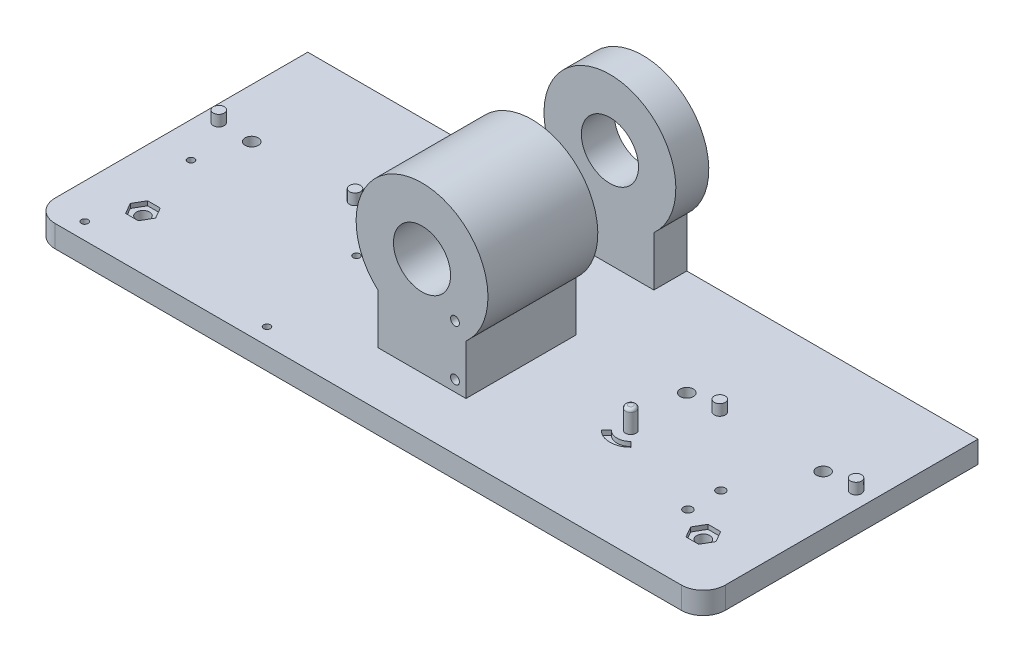
SolidWorks part; units mm, degrees
ref_plane "Front Plane" through (0, 0, 0) normal (0, 0, 1) x (1, 0, 0)
ref_plane "Top Plane" through (0, 0, 0) normal (0, 1, 0) x (1, 0, 0)
ref_plane "Right Plane" through (0, 0, 0) normal (1, 0, 0) x (0, 0, -1)
sketch "Sketch1" plane through (0, 0, 0) normal (0, 1, 0) x (1, 0, 0)
  line L0 (152.5, 125) -> (152.5, 0) construction
  line L1 (0, 0) -> (305, 0)
  line L2 (0, 0) -> (0, 125)
  line L3 (0, 125) -> (305, 125)
  line L4 (305, 0) -> (305, 125)
  line L5 (25, 100) -> (280, 100) construction
  line L6 (280, 25) -> (280, 100) construction
  line L7 (25, 25) -> (280, 25) construction
  line L8 (25, 25) -> (25, 100) construction
  line L9 (152.5, 62.5) -> (25, 62.5) construction
  line L10 (30.7735, 100) -> (27.8868, 105) construction
  line L11 (27.8868, 105) -> (22.1132, 105) construction
  line L12 (22.1132, 105) -> (19.2265, 100) construction
  line L13 (19.2265, 100) -> (22.1132, 95) construction
  line L14 (22.1132, 95) -> (27.8868, 95) construction
  line L15 (27.8868, 95) -> (30.7735, 100) construction
  line L16 (27.8868, 30) -> (30.7735, 25) construction
  line L17 (22.1132, 30) -> (27.8868, 30) construction
  line L18 (19.2265, 25) -> (22.1132, 30) construction
  line L19 (22.1132, 20) -> (19.2265, 25) construction
  line L20 (27.8868, 20) -> (22.1132, 20) construction
  line L21 (30.7735, 25) -> (27.8868, 20) construction
  line L22 (282.8868, 30) -> (277.1132, 30) construction
  line L23 (285.7735, 25) -> (282.8868, 30) construction
  line L24 (282.8868, 20) -> (285.7735, 25) construction
  line L25 (277.1132, 20) -> (282.8868, 20) construction
  line L26 (274.2265, 25) -> (277.1132, 20) construction
  line L27 (277.1132, 30) -> (274.2265, 25) construction
  line L28 (277.1132, 95) -> (274.2265, 100) construction
  line L29 (282.8868, 95) -> (277.1132, 95) construction
  line L30 (285.7735, 100) -> (282.8868, 95) construction
  line L31 (282.8868, 105) -> (285.7735, 100) construction
  line L32 (277.1132, 105) -> (282.8868, 105) construction
  line L33 (274.2265, 100) -> (277.1132, 105) construction
  line L34 (172.5, 75) -> (172.5, 125) construction
  line L35 (132.5, 0) -> (172.5, 0) construction
  line L36 (132.5, 0) -> (132.5, 125) construction
  line L37 (132.5, 125) -> (172.5, 125) construction
  line L38 (172.5, 0) -> (172.5, 125) construction
  line L39 (132.5, 75) -> (172.5, 75) construction
  line L40 (132.5, 75) -> (132.5, 25) construction
  line L41 (132.5, 25) -> (172.5, 25) construction
  line L42 (172.5, 75) -> (172.5, 25) construction
  line L50 (305, 14.5) -> (253.3, 14.5) construction
  line L51 (0, 84.5) -> (15, 69.5) construction
  line L52 (132.5, 75) -> (117.5, 60) construction
  line L53 (117.5, 60) -> (117.5, 85) construction
  line L54 (0, 125) -> (108, 125) construction
  line L55 (0, 125) -> (0, 84.5) construction
  line L56 (0, 84.5) -> (108, 84.5) construction
  line L57 (108, 125) -> (108, 84.5) construction
  line L58 (15, 69.5) -> (15, 84.5) construction
  line L59 (30, 84.5) -> (0, 84.5) construction
  line L60 (30, 84.5) -> (30, 69.5) construction
  line L61 (30, 69.5) -> (0, 69.5) construction
  line L62 (0, 84.5) -> (0, 69.5) construction
  line L63 (92, 84.5) -> (92, 69.5) construction
  line L64 (62, 0) -> (62, 125) construction
  line L65 (253.3, 14.5) -> (253.3, 0) construction
  line L66 (253.3, 38.75) -> (280.2, 38.75) construction
  line L67 (253.3, 14.5) -> (280.2, 14.5) construction
  line L68 (253.3, 14.5) -> (253.3, 63) construction
  line L69 (253.3, 63) -> (280.2, 63) construction
  line L70 (280.2, 14.5) -> (280.2, 63) construction
  line L71 (266.75, 31.25) -> (266.75, 38.75) construction
  circle A1 centre (25, 100) radius 5 construction
  circle A3 centre (280, 25) radius 3
  circle A4 centre (25, 25) radius 3
  circle A8 centre (117.5, 60) radius 3
  circle A9 centre (117.5, 85) radius 3
  circle A10 centre (7.5, 77) radius 3 construction
  circle A11 centre (22.5, 77) radius 3
  circle A12 centre (69.5, 77) radius 3 construction
  circle A13 centre (84.5, 77) radius 3
  circle A14 centre (220.5, 77) radius 3
  circle A15 centre (235.5, 77) radius 3 construction
  circle A16 centre (282.5, 77) radius 3
  circle A17 centre (297.5, 77) radius 3 construction
  circle A18 centre (266.75, 31.25) radius 2
  circle A19 centre (266.75, 46.25) radius 2
  dimension "D3" = 6
  dimension "D22" = 4
  dimension "D1" = 305
  dimension "D2" = 125
  dimension "D5" = 10
  dimension "D6" = 40
  dimension "D8" = 50
  dimension "D12" = 15
  dimension "D7" = 40.5
  dimension "D9" = 108
  dimension "D10" = 15
  dimension "D11" = 30
  dimension "D15" = 62
  dimension "D16" = 15
  dimension "D17" = 25
  dimension "D18" = 51.7
  dimension "D19" = 14.5
  dimension "D20" = 26.9
  dimension "D21" = 48.5
  dimension "D23" = 7.5
  dimension "D4" = 25
  dimension "D13" = 2
  dimension "D14" = 2
extrude "Boss-Extrude1" add sketch "Sketch1" along normal blind 10
sketch "Sketch7" plane through (0, 10, 0) normal (0, 1, 0) x (1, 0, 0)
  line L0 (0, 0) -> (305, 0) construction
  line L1 (132.5, 24.5) -> (172.5, 24.5)
  line L2 (132.5, 24.5) -> (132.5, 74.5)
  line L3 (132.5, 74.5) -> (172.5, 74.5)
  line L4 (172.5, 24.5) -> (172.5, 74.5)
  line L5 (152.5, 0) -> (152.5, 125) construction
  line L6 (305, 125) -> (0, 125) construction
  line L18 (132.5, 110) -> (172.5, 110)
  line L19 (132.5, 110) -> (132.5, 125)
  line L20 (132.5, 125) -> (172.5, 125)
  line L21 (172.5, 110) -> (172.5, 125)
  point P11 (152.5, 74.5)
  point P20 (152.5, 110)
  dimension "D1" = 40
  dimension "D2" = 50
  dimension "D4" = 15
  dimension "D3" = 35.5
extrude "Boss-Extrude2" add sketch "Sketch7" along normal blind 22.6393
sketch "Sketch11" plane through (0, 0, -24.5) normal (0, 0, 1) x (1, 0, 0)
  circle A0 centre (152.5, 55) radius 30
  circle A1 centre (152.5, 55) radius 13
  dimension "D1" = 60
  dimension "D2" = 26
extrude "Boss-Extrude3" add sketch "Sketch11" against normal up to surface (100.5 mm away) up to face at (152.5, 13.1598, -125)
ref_plane "Plane1" through (0, 0, -62.5) normal (0, 0, 1) x (1, 0, 0)
sketch "Sketch12" plane through (305, 0, 0) normal (1, 0, 0) x (0, 0, -1)
  line L0 (125, 85) -> (24.5, 85) construction
  line L1 (74.5, 10) -> (110, 10)
  line L2 (74.5, 10) -> (74.5, 85)
  line L3 (74.5, 85) -> (110, 85)
  line L4 (110, 10) -> (110, 85)
  line L6 (110, 32.6393) -> (110, 10) construction
extrude "Cut-Extrude2" cut sketch "Sketch12" against normal through all
sketch "Sketch13" plane through (0, 10, 0) normal (0, 1, 0) x (1, 0, 0)
  line L0 (222.5, 49.5) -> (172.5, 49.5) construction
  line L1 (172.5, 24.5) -> (172.5, 74.5) construction
  circle A1 centre (222.5, 49.5) radius 2.4
  dimension "D1" = 4.8
  dimension "D2" = 50
extrude "Boss-Extrude4" add sketch "Sketch13" along normal blind 10
sketch "Sketch6" plane through (0, 10, 0) normal (0, 1, 0) x (1, 0, 0)
  line L0 (152.5, 125) -> (152.5, 0) construction
  line L7 (215.7825, 42.7825) -> (218.0806, 45.0806)
  line L8 (0, 0) -> (305, 0) construction
  line L9 (152.5, 62.5) -> (0, 62.5) construction
  line L10 (0, 125) -> (0, 0) construction
  line L29 (27.8868, 30) -> (30.7735, 25)
  line L30 (274.2265, 25) -> (277.1132, 20)
  line L31 (277.1132, 20) -> (282.8868, 20)
  line L32 (282.8868, 20) -> (285.7735, 25)
  line L33 (285.7735, 25) -> (282.8868, 30)
  line L34 (282.8868, 30) -> (277.1132, 30)
  line L35 (277.1132, 30) -> (274.2265, 25)
  line L36 (22.1132, 30) -> (27.8868, 30)
  line L37 (19.2265, 25) -> (22.1132, 30)
  line L38 (22.1132, 20) -> (19.2265, 25)
  line L39 (27.8868, 20) -> (22.1132, 20)
  line L40 (30.7735, 25) -> (27.8868, 20)
  line L41 (231.3388, 40.6612) -> (213.6612, 58.3388) construction
  line L42 (213.6612, 40.6612) -> (231.3388, 58.3388) construction
  line L43 (222.5, 49.5) -> (222.5, 37) construction
  line L44 (213.6612, 40.6612) -> (222.5, 37) construction
  line L45 (222.5, 37) -> (231.3388, 40.6612) construction
  line L46 (229.2175, 42.7825) -> (226.9194, 45.0806)
  circle A0 centre (280, 25) radius 5 construction
  circle A1 centre (222.5, 49.5) radius 12.5 construction
  circle A2 centre (222.5, 49.5) radius 9.5 construction
  circle A3 centre (222.5, 49.5) radius 6.25 construction
  arc A4 (218.0806, 45.0806) -> (226.9194, 45.0806) centre (222.5, 49.5) ccw
  arc A5 (215.7825, 42.7825) -> (229.2175, 42.7825) centre (222.5, 49.5) ccw
  dimension "D2" = 25
  dimension "D4" = 12.5
  dimension "D1" = 10
  dimension "D3" = 3
extrude "Cut-Extrude1" cut sketch "Sketch6" against normal blind 2
fillet "Fillet1" radius 1.3 1 edges at (222.5, 20, -47.1)
sketch "Sketch15" plane through (0, 10, 0) normal (0, 1, 0) x (1, 0, 0)
  line L0 (69.5, 77) -> (7.5, 77) construction
  line L1 (38.5, 77) -> (38.5, 84.5) construction
  line L2 (0, 84.5) -> (108, 84.5) construction
  line L3 (152.5, 125) -> (152.5, 0) construction
  circle A1 centre (69.5, 77) radius 2.5
  circle A2 centre (7.5, 77) radius 2.5
  circle A3 centre (7.5, 77) radius 2.5
  circle A4 centre (235.5, 77) radius 2.5
  circle A5 centre (297.5, 77) radius 2.5
  dimension "D1" = 0.5
extrude "Boss-Extrude5" add sketch "Sketch15" along normal blind 5
sketch "Sketch16" plane through (0, 10, 0) normal (0, 1, 0) x (1, 0, 0)
  line L0 (0, 0) -> (305, 0) construction
  line L1 (0, 125) -> (0, 0) construction
  circle A0 centre (16, 7.5) radius 1.55
  circle A1 centre (98.95, 7.5) radius 1.55
  circle A2 centre (16, 55.866) radius 1.55
  circle A3 centre (91.33, 55.866) radius 1.55
  point P16 (198.1287, 12.0364)
  dimension "D1" = 3.1
  dimension "D2" = 7.5
  dimension "D3" = 82.95
  dimension "D4" = 16
  dimension "D5" = 48.366
  dimension "D6" = 75.33
extrude "Cut-Extrude3" cut sketch "Sketch16" against normal through all
chamfer "Chamfer1" distance 3.3 angle 45 6 edges at (282.5, 0, -74) (220.5, 0, -74) (84.5, 0, -80) (22.5, 0, -80) (117.5, 0, -57) (117.5, 0, -82)
fillet "Fillet3" radius 10 2 edges at (305, 5, 0) (0, 5, 0)
fillet "Fillet2" [suppressed] radius 0.5
chamfer "Chamfer2" distance 1.65 4 edges at (98.95, 0, -5.95) (91.33, 0, -54.316) (16, 0, -5.95) (16, 0, -54.316)
sketch "Sketch17" plane through (0, 0, -24.5) normal (0, 0, 1) x (1, 0, 0)
  line L0 (167.5, 15) -> (167.5, 38.11) construction
  line L2 (172.5, 10) -> (167.5, 15) construction
  circle A0 centre (167.5, 15) radius 2
  circle A1 centre (167.5, 38.11) radius 2
  dimension "D2" = 4
  dimension "D1" = 23.11
  dimension "D3" = 5
  dimension "D4" = 5
extrude "Cut-Extrude4" cut sketch "Sketch17" against normal up to next
equation "\"joint_width\"=4"
equation "\"short_base_length\"=12.5"
equation "\"D2@Sketch1\"=\"short_base_length\""
equation "\"outer_diam_main_joint\"=6"
equation "\"D1@Sketch11\"=\"outer_diam_main_joint\""
equation "\"D1@Sketch7\"=\"outer_diam_main_joint\"-2"
equation "\"D1@Boss-Extrude2\"=(\"outer_diam_main_joint\"/2)+1.5cm-sqr((\"outer_diam_main_joint\"/2)^2-((\"outer_diam_main_joint\"-2)/2)^2)"
equation "\"D6@Sketch1\"=\"outer_diam_main_joint\"-2"
equation "\"pulleyside\"=1.5"
